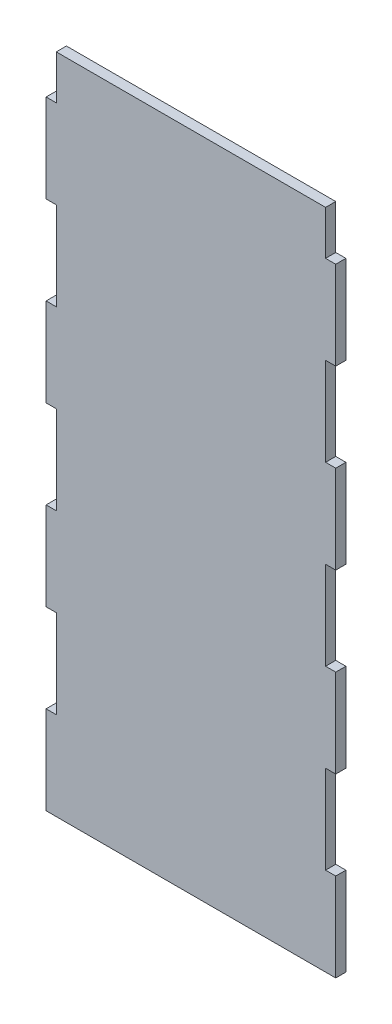
SolidWorks part; units mm, degrees
ref_plane "Front Plane" through (0, 0, 0) normal (0, 0, 1) x (1, 0, 0)
ref_plane "Top Plane" through (0, 0, 0) normal (0, 1, 0) x (1, 0, 0)
ref_plane "Right Plane" through (0, 0, 0) normal (1, 0, 0) x (0, 0, -1)
sketch "Sketch1" plane through (0, 0, 0) normal (0, 0, 1) x (1, 0, 0)
  line L1 (-41.656, 95.25) -> (41.656, 95.25)
  line L2 (-41.656, 95.25) -> (-41.656, -95.25)
  line L3 (-41.656, -95.25) -> (41.656, -95.25)
  line L4 (41.656, 95.25) -> (41.656, -95.25)
  point P4 (0, 95.25)
  point P6 (-41.656, 0)
  dimension "D1" = 83.312
  dimension "D2" = 190.5
extrude "Boss-Extrude1" add sketch "Sketch1" along normal mid plane 2.921
sketch "Sketch2" plane through (0, 0, 1.4605) normal (0, 0, 1) x (1, 0, 0)
  line L0 (-38.735, -95.25) -> (38.735, -95.25)
  line L1 (-41.656, 95.25) -> (41.656, 95.25)
  line L2 (-41.656, 95.25) -> (-41.656, -95.25)
  line L3 (-41.656, -95.25) -> (-38.735, -95.25)
  line L4 (41.656, 95.25) -> (41.656, -95.25)
  line L5 (38.735, -95.25) -> (41.656, -95.25)
  line L6 (-41.656, 95.25) -> (-38.735, 95.25)
  line L7 (-41.656, 95.25) -> (-41.656, -95.25)
  line L8 (-41.656, -95.25) -> (-38.735, -95.25)
  line L9 (-38.735, 95.25) -> (-38.735, -95.25)
  line L10 (41.656, 95.25) -> (38.735, 95.25)
  line L11 (41.656, 95.25) -> (41.656, -95.25)
  line L12 (41.656, -95.25) -> (38.735, -95.25)
  line L13 (38.735, 95.25) -> (38.735, -95.25)
  line L14 (-41.656, -69.85) -> (-38.735, -69.85)
  line L15 (38.735, -69.85) -> (41.656, -69.85)
  line L16 (-41.656, -44.45) -> (-38.735, -44.45)
  line L17 (38.735, -44.45) -> (41.656, -44.45)
  line L18 (-41.656, -19.05) -> (-38.735, -19.05)
  line L19 (38.735, -19.05) -> (41.656, -19.05)
  line L20 (-41.656, 6.35) -> (-38.735, 6.35)
  line L21 (38.735, 6.35) -> (41.656, 6.35)
  line L22 (-41.656, 31.75) -> (-38.735, 31.75)
  line L23 (38.735, 31.75) -> (41.656, 31.75)
  line L24 (-41.656, 57.15) -> (-38.735, 57.15)
  line L25 (38.735, 57.15) -> (41.656, 57.15)
  line L26 (-41.656, -95.25) -> (-41.656, -69.85) construction
  line L27 (-41.656, 82.55) -> (-38.735, 82.55)
  line L28 (0, 95.25) -> (0, -95.25) construction
  line L29 (41.656, 82.55) -> (38.735, 82.55)
  point P42 (4.9406, -104.5312)
  point P43 (0, -95.25)
  line M13 (-41.656, 95.25) -> (-41.656, -95.25)
  line M16 (41.656, 95.25) -> (-41.656, 95.25)
  dimension "D1" = 2.921
  dimension "D2" = 2.921
  dimension "D4" = 25.4
  dimension "D5" = 2.921
  dimension "D6" = 2.921
  dimension "D7" = 25.4
  dimension "D3" = 7
extrude "Cut-Extrude1" cut sketch "Sketch2" against normal blind 2.921 contours L24 L7 L22 L9 | L20 L7 L18 L9 | L16 L7 L14 L9 | L17 L13 L15 L11 | L21 L13 L19 L11 | L25 L13 L23 L11 | L27 L9 L1 M13 | L29 L11 L13 M16 region at (-40.1955, -57.15, 1.4605) region at (40.1955, -57.15, 1.4605) region at (-40.1955, -6.35, 1.4605) region at (40.1955, -6.35, 1.4605) region at (-40.1955, 44.45, 1.4605) region at (40.1955, 44.45, 1.4605) region at (-40.1955, 88.9, 1.4605) region at (40.1955, 88.9, 1.4605)
